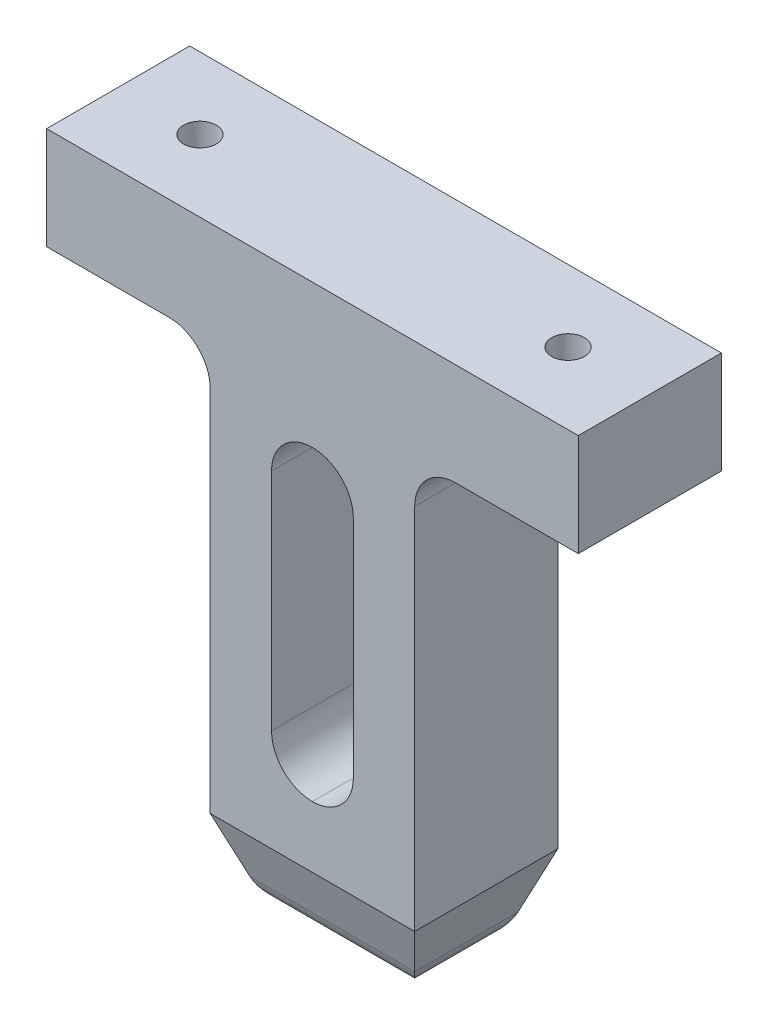
SolidWorks part; units mm, degrees
ref_plane "Front Plane" through (0, 0, 0) normal (0, 0, 1) x (1, 0, 0)
ref_plane "Top Plane" through (0, 0, 0) normal (0, 1, 0) x (1, 0, 0)
ref_plane "Right Plane" through (0, 0, 0) normal (1, 0, 0) x (0, 0, -1)
sketch "Sketch1" plane through (0, 0, 0) normal (1, 0, 0) x (0, 0, -1)
  line L0 (0, 0) -> (0, 2.5) construction
  line L8 (-3.5, 2.5) -> (3.5, 2.5)
  line L9 (-3.5, 2.5) -> (-3.5, -2.5)
  line L10 (-3.5, -2.5) -> (3.5, -2.5)
  line L11 (3.5, 2.5) -> (3.5, -2.5)
  line L12 (-3.5, 2.5) -> (3.5, -2.5) construction
  line L13 (-3.5, -2.5) -> (3.5, 2.5) construction
  point P5 (0, 0)
  dimension "D1" = 5
  dimension "D2" = 7
extrude "Boss-Extrude1" add sketch "Sketch1" along normal blind 26
sketch "Sketch2" plane through (0, 2.5, -8.0472) normal (0, -1, 0) x (1, 0, 0)
  line L0 (0, 8.0472) -> (26, 8.0472) construction
  line L1 (26, 11.5472) -> (0, 11.5472) construction
  line L3 (4, 8.0472) -> (22, 8.0472)
  point P2 (0, 0)
  point P9 (13, 8.0472)
  dimension "D1" = 3.5
sketch "Sketch3" plane through (0, 2.5, -8.0472) normal (0, -1, 0) x (1, 0, 0)
  circle A0 centre (4, 8.0472) radius 0.8
  circle A1 centre (22, 8.0472) radius 0.8
extrude "Cut-Extrude1" cut sketch "Sketch3" along normal blind 7
sketch "Sketch4" plane through (0, -2.5, 0) normal (0, -1, 0) x (1, 0, 0)
  line L0 (26, 0) -> (0, 0) construction
  line L1 (26, 3.5) -> (26, -3.5) construction
  line L2 (0, 3.5) -> (0, -3.5) construction
  line L3 (26, -3.5) -> (0, -3.5) construction
  line L4 (18, 3.5) -> (8, 3.5)
  line L5 (18, 3.5) -> (18, -3.5)
  line L6 (18, -3.5) -> (8, -3.5)
  line L7 (8, 3.5) -> (8, -3.5)
  line L8 (18, 3.5) -> (8, -3.5) construction
  line L9 (18, -3.5) -> (8, 3.5) construction
  point P6 (13, 0)
  dimension "D1" = 10
extrude "Boss-Extrude2" add sketch "Sketch4" along normal blind 20
sketch "Sketch5" plane through (0, 0, 3.5) normal (0, 0, 1) x (1, 0, 0)
  line L0 (18, -22.5) -> (8, -22.5) construction
  line L4 (8, -22.5) -> (8, -2.5) construction
  line L5 (15, -4.5) -> (11, -4.5)
  line L6 (15, -4.5) -> (15, -19.5)
  line L7 (15, -19.5) -> (11, -19.5)
  line L8 (11, -4.5) -> (11, -19.5)
  line L9 (18, -22.5) -> (18, -2.5) construction
  line L10 (26, -2.5) -> (18, -2.5) construction
  point P6 (12.8423, -17.8859)
  dimension "D1" = 3
  dimension "D2" = 3
  dimension "D3" = 3
  dimension "D4" = 2
extrude "Cut-Extrude2" cut sketch "Sketch5" against normal blind 20
sketch "Sketch6" plane through (0, -22.5, 0) normal (0, -1, 0) x (1, 0, 0)
  line L5 (18, 3.5) -> (8, 3.5)
  line L6 (18, 3.5) -> (18, -3.5)
  line L7 (18, -3.5) -> (8, -3.5)
  line L8 (8, 3.5) -> (8, -3.5)
extrude "Boss-Extrude3" add sketch "Sketch6" along normal blind 4 draft 20 separate body
fillet "Fillet2" radius 2 4 edges at (15, -4.5, 0) (11, -4.5, 0) (15, -19.5, 0) (11, -19.5, 0)
fillet "Fillet5" radius 2 2 edges at (18, -2.5, 0) (8, -2.5, 0)
fillet "Fillet8" radius 2 4 edges at (13, -26.5, -2.0441) (9.4559, -26.5, 0) (13, -26.5, 2.0441) (16.5441, -26.5, 0)
